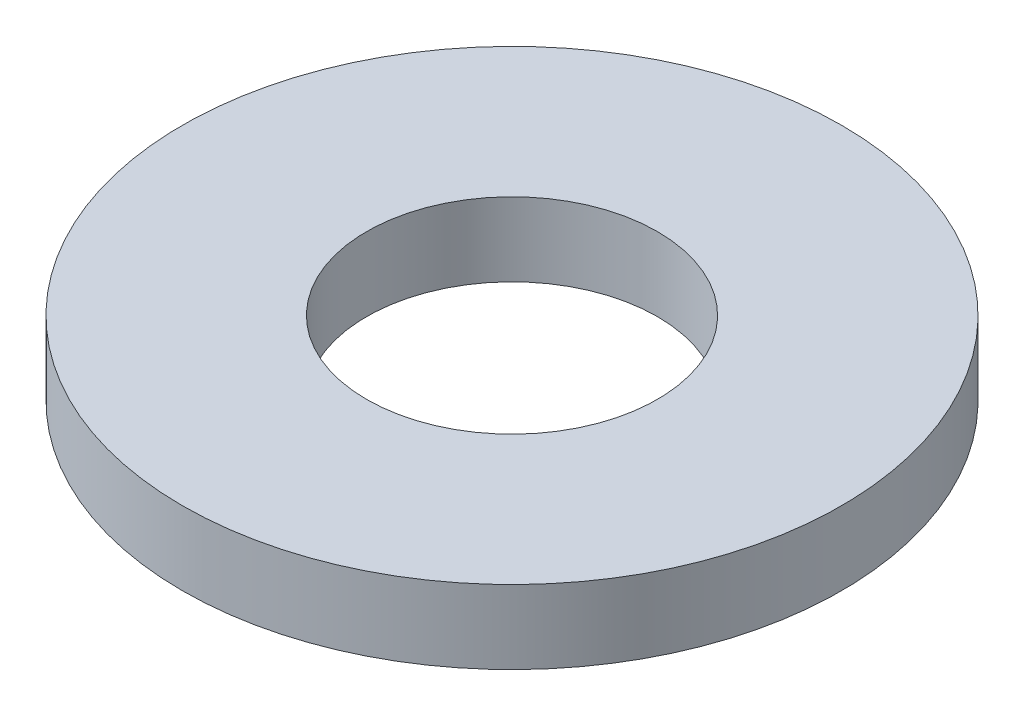
SolidWorks part; units mm, degrees
ref_plane "Front Plane" through (0, 0, 0) normal (0, 0, 1) x (1, 0, 0)
ref_plane "Top Plane" through (0, 0, 0) normal (0, 1, 0) x (1, 0, 0)
ref_plane "Right Plane" through (0, 0, 0) normal (1, 0, 0) x (0, 0, -1)
sketch "Sketch1" plane through (0, 0, 0) normal (0, 1, 0) x (1, 0, 0)
  circle A0 centre (0, 0) radius 85
  dimension "FLANGE_OD" = 170
extrude "Boss-Extrude1" add sketch "Sketch1" along normal blind 19
sketch "Sketch2" plane through (0, 0, 0) normal (0, 1, 0) x (1, 0, 0)
  circle A0 centre (0, 0) radius 37.5
  dimension "BORE_D" = 75
extrude "Cut-Extrude1" cut sketch "Sketch2" along normal through all
sketch "Sketch3" plane through (0, 19, 0) normal (0, 1, 0) x (1, 0, 0)
  circle A0 centre (0, 0) radius 29.7688 construction
  circle A1 centre (-29.7688, 0) radius 3.4787
  dimension "BOLT_D" = 6.9574
  dimension "BOLT_PCD" = 59.5376
extrude "Cut-Extrude2" cut sketch "Sketch3" against normal blind 15.835 rebuild error yes
pattern_circular "CirPattern1" count 3 over 360 rebuild error yes
